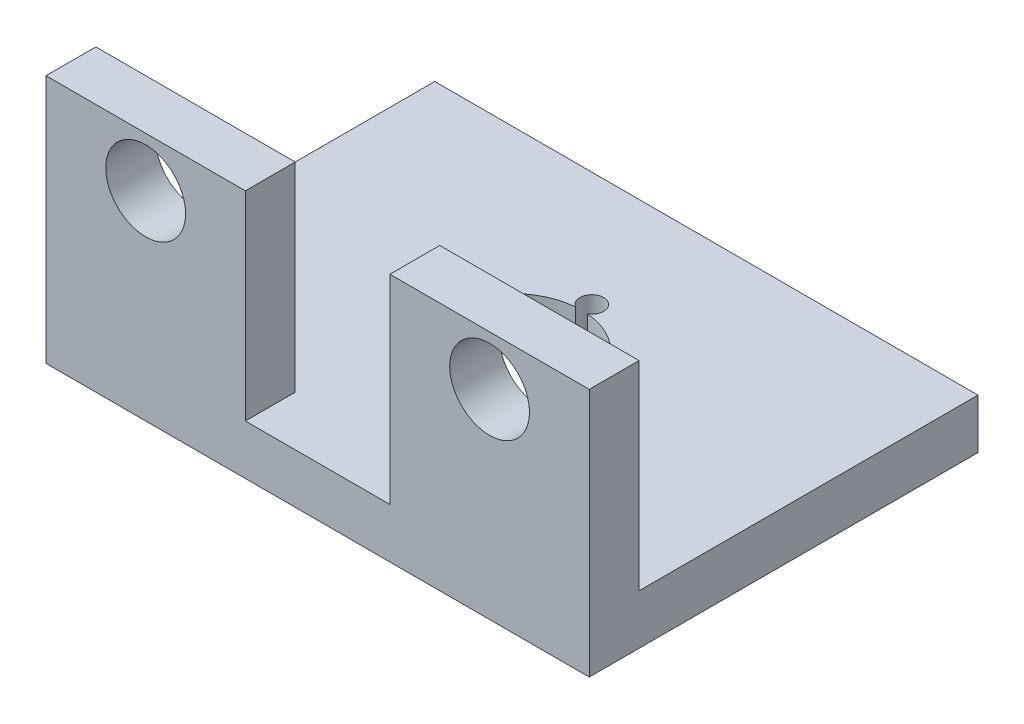
SolidWorks part; units mm, degrees
ref_plane "Front Plane" through (0, 0, 0) normal (0, 0, 1) x (1, 0, 0)
ref_plane "Top Plane" through (0, 0, 0) normal (0, 1, 0) x (1, 0, 0)
ref_plane "Right Plane" through (0, 0, 0) normal (1, 0, 0) x (0, 0, -1)
sketch "Sketch1" plane through (0, 0, 0) normal (0, 1, 0) x (1, 0, 0)
  line L1 (-40.6495, -11.3707) -> (13.8505, -11.3707)
  line L2 (-40.6495, -11.3707) -> (-40.6495, 27.6293)
  line L3 (-40.6495, 27.6293) -> (13.8505, 27.6293)
  line L4 (13.8505, -11.3707) -> (13.8505, 27.6293)
  dimension "D1" = 54.5
  dimension "D2" = 39
extrude "Boss-Extrude1" add sketch "Sketch1" along normal blind 5
sketch "Sketch10" plane through (0, 5, 0) normal (0, 1, 0) x (1, 0, 0)
  line L1 (13.8505, -11.3707) -> (13.8505, 27.6293) construction
  line L2 (-40.6495, -11.3707) -> (13.8505, -11.3707) construction
  circle A0 centre (-13.3995, 8.1293) radius 7
  dimension "D1" = 27.25
  dimension "D2" = 19.5
extrude "Cut-Extrude1" cut sketch "Sketch10" against normal blind 5 contours A0
hole_wizard "M2 Clearance Hole1" positions "3DSketch1" profile "Sketch11" hole size "M2" standard "ANSI Metric"
sketch3d "3DSketch1"
  line L0 (13.8505, 5, 11.3707) -> (13.8505, 5, -27.6293) construction
  line L1 (-40.6495, 5, 11.3707) -> (13.8505, 5, 11.3707) construction
  line L2 (-40.6495, 5, -27.6293) -> (-40.6495, 5, 11.3707) construction
  point P0 (-13.3995, 5, -0.1293)
  point P2 (-5.4048, 5, -8.1293)
  point P4 (-21.3943, 5, -8.1293)
  point P6 (-13.3995, 5, -16.1293)
  dimension "D1" = 16
  dimension "D2" = 11.31
  dimension "D3" = 11.31
  dimension "D4" = 11.31
  dimension "D5" = 11.31
  dimension "D6" = 27.25
  dimension "D7" = 27.25
  dimension "D8" = 11.5
  dimension "D9" = 19.2552
  dimension "D10" = 19.2552
sketch "Sketch11" plane through (-13.3995, 5, -0.1293) normal (1, 0, 0) x (0, 0, 1)
  line L0 (0, 0) -> (0, 17.721)
  line L1 (0, 17.721) -> (1.2, 17)
  line L2 (1.2, 17) -> (1.2, 0)
  line L5 (1.2, 0) -> (0, 0)
  line L10 (0, 17.721) -> (-1.2, 17) construction
  line L11 (0, -6.35) -> (0, 107.95) construction
  dimension "Hole Dia." = 2.4
  dimension "Hole Depth" = 17
  dimension "Drill Angle" = 118
sketch "Sketch12" plane through (0, 5, 0) normal (0, 1, 0) x (1, 0, 0)
  line L1 (13.8505, -11.3707) -> (-6.1495, -11.3707)
  line L2 (13.8505, -11.3707) -> (13.8505, -6.3707)
  line L3 (13.8505, -6.3707) -> (-6.1495, -6.3707)
  line L4 (-6.1495, -11.3707) -> (-6.1495, -6.3707)
  line L5 (-40.6495, -11.3707) -> (-20.6495, -11.3707)
  line L6 (-40.6495, -11.3707) -> (-40.6495, -6.3707)
  line L7 (-40.6495, -6.3707) -> (-20.6495, -6.3707)
  line L8 (-20.6495, -11.3707) -> (-20.6495, -6.3707)
  dimension "D1" = 20
  dimension "D2" = 20
  dimension "D3" = 5
  dimension "D4" = 5
extrude "Boss-Extrude2" add sketch "Sketch12" along normal blind 20
sketch "Sketch13" plane through (0, 0, 6.3707) normal (0, 0, -1) x (-1, 0, 0)
  line L1 (-13.8505, 25) -> (-13.8505, 5) construction
  line L2 (40.6495, 25) -> (40.6495, 5) construction
  line L3 (-13.8505, 5) -> (6.1495, 5) construction
  line L4 (20.6495, 5) -> (40.6495, 5) construction
  circle A0 centre (-3.8505, 20) radius 4
  circle A1 centre (30.6495, 20) radius 4
  dimension "D1" = 10
  dimension "D2" = 10
  dimension "D3" = 15
  dimension "D4" = 15
extrude "Cut-Extrude2" cut sketch "Sketch13" against normal blind 5
